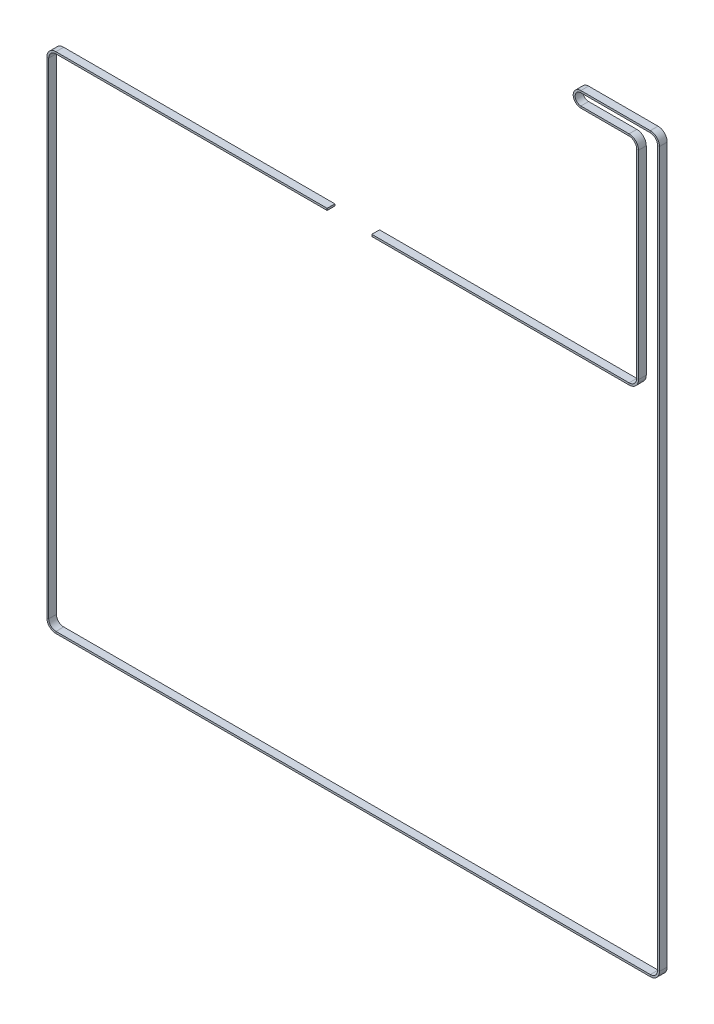
SolidWorks part; units mm, degrees
ref_plane "Front" through (0, 0, 0) normal (0, 0, 1) x (1, 0, 0)
ref_plane "Top" through (0, 0, 0) normal (0, 1, 0) x (1, 0, 0)
ref_plane "Right" through (0, 0, 0) normal (1, 0, 0) x (0, 0, -1)
sketch "Sketch1" plane through (0, 0, 2.2) normal (0, 0, 1) x (1, 0, 0)
  line L0 (377.3122, -142.2854) -> (431.3122, -142.2854)
  line L1 (377.3122, -152.6854) -> (414.8122, -152.6854)
  line L2 (421.4122, -159.2854) -> (421.4122, -313.704)
  line L3 (437.6872, -148.6604) -> (437.6872, -703.9854)
  line L4 (-37.0628, -703.9854) -> (-37.0628, -326.529)
  line L5 (431.3122, -710.3604) -> (-30.6878, -710.3604)
  line L6 (-30.6878, -320.154) -> (180.1133, -320.154)
  line L8 (214.8133, -320.204) -> (214.8133, -323.704) construction
  line L9 (414.8122, -320.304) -> (214.8133, -320.304)
  line L11 (180.1133, -320.204) -> (180.1133, -323.704) construction
  circle A0 centre (414.8122, -159.2854) radius 6.6 construction
  circle A1 centre (431.3122, -148.6604) radius 6.375 construction
  circle A2 centre (377.3122, -147.4854) radius 5.2 construction
  arc A3 (431.3122, -142.2854) -> (437.6872, -148.6604) centre (431.3122, -148.6604) cw
  arc A4 (377.3122, -152.6854) -> (377.3122, -142.2854) centre (377.3122, -147.4854) cw
  arc A5 (414.8122, -152.6854) -> (421.4122, -159.2854) centre (414.8122, -159.2854) cw
  circle A6 centre (-30.6878, -703.9854) radius 6.375 construction
  arc A7 (-30.6878, -710.3604) -> (-37.0628, -703.9854) centre (-30.6878, -703.9854) cw
  circle A8 centre (431.3122, -148.6604) radius 9 construction
  circle A9 centre (414.8122, -159.2854) radius 9 construction
  circle A11 centre (431.3122, -703.9854) radius 6.375 construction
  arc A12 (437.6872, -703.9854) -> (431.3122, -710.3604) centre (431.3122, -703.9854) cw
  arc A13 (-37.0628, -326.529) -> (-30.6878, -320.154) centre (-30.6878, -326.529) cw
  arc A15 (421.4122, -313.704) -> (414.8122, -320.304) centre (414.8122, -313.704) cw
  circle A16 centre (-30.6878, -326.529) radius 6.375 construction
  circle A17 centre (-30.6878, -326.529) radius 5.9875 construction
  circle A18 centre (414.8122, -313.704) radius 6.6 construction
  circle A19 centre (414.8122, -313.704) radius 5.9875 construction
  dimension "D1" = 12.75
ref_plane "Plane1" through (180.1133, -320.154, 2.2) normal (1, 0, 0) x (0, 0, -1)
sketch "Sketch4" plane through (180.1133, -320.154, 2.2) normal (1, 0, 0) x (0, 0, -1)
  line L0 (0, 171.4936) -> (0, -383.8314) construction
  line L1 (3, -0.75) -> (-3, -0.75)
  line L2 (3, -0.75) -> (3, 0.75)
  line L3 (3, 0.75) -> (-3, 0.75)
  line L4 (-3, -0.75) -> (-3, 0.75)
  line L5 (3, -0.75) -> (-3, 0.75) construction
  line L6 (3, 0.75) -> (-3, -0.75) construction
  point P0 (0, 0)
  dimension "D1" = 1.5
  dimension "D2" = 6
sweep "Sweep1" add profiles "Sketch4" path "Sketch1"
